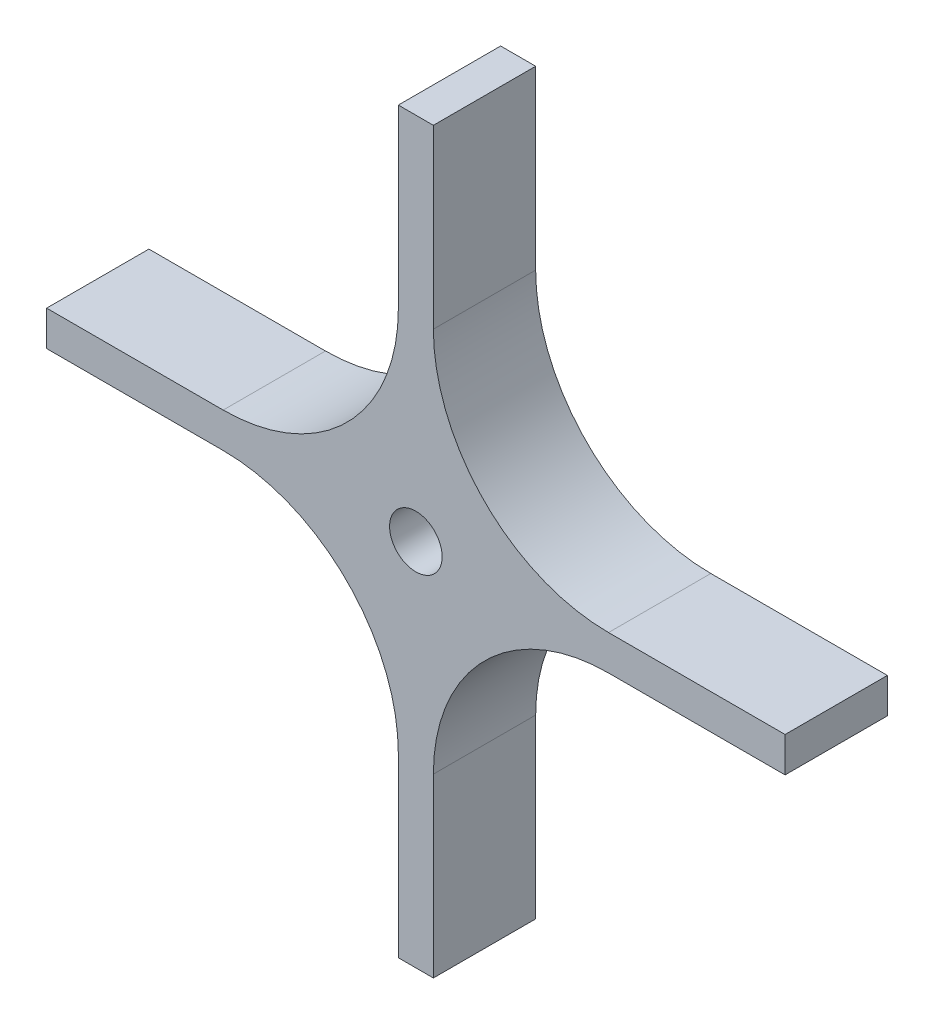
SolidWorks part; units mm, degrees
ref_plane "Front Plane" through (0, 0, 0) normal (0, 0, 1) x (1, 0, 0)
ref_plane "Top Plane" through (0, 0, 0) normal (0, 1, 0) x (1, 0, 0)
ref_plane "Right Plane" through (0, 0, 0) normal (1, 0, 0) x (0, 0, -1)
sketch "Sketch1" plane through (0, 0, 0) normal (0, 0, 1) x (1, 0, 0)
  line L0 (1.5875, -1.5875) -> (1.5875, -33.4645)
  line L1 (-1.5875, 33.4645) -> (1.5875, 33.4645)
  line L2 (-1.5875, 33.4645) -> (-1.5875, 1.5875)
  line L3 (-1.5875, -33.4645) -> (1.5875, -33.4645)
  line L4 (1.5875, 33.4645) -> (1.5875, 1.5875)
  line L5 (-1.5875, 33.4645) -> (1.5875, -33.4645) construction
  line L6 (-1.5875, -33.4645) -> (1.5875, 33.4645) construction
  line L7 (-33.4645, 1.5875) -> (-1.5875, 1.5875)
  line L8 (-33.4645, 1.5875) -> (-33.4645, -1.5875)
  line L9 (-33.4645, -1.5875) -> (-1.5875, -1.5875)
  line L10 (33.4645, 1.5875) -> (33.4645, -1.5875)
  line L11 (-33.4645, 1.5875) -> (33.4645, -1.5875) construction
  line L12 (-33.4645, -1.5875) -> (33.4645, 1.5875) construction
  line L13 (1.5875, -1.5875) -> (33.4645, -1.5875)
  line L14 (1.5875, 1.5875) -> (33.4645, 1.5875)
  line L15 (-1.5875, -1.5875) -> (-1.5875, -33.4645)
  circle A0 centre (17.526, 17.526) radius 15.9385 construction
  circle A1 centre (0, 0) radius 42.8625 construction
  point P0 (0, 0)
  point P6 (0, 0)
  point P21 (0, 0)
  point P22 (0, 0)
  dimension "D3" = 31.877
  dimension "D4" = 85.725
  dimension "D1" = 3.175
  dimension "D2" = 3.175
extrude "Boss-Extrude1" add sketch "Sketch1" along normal mid plane 9.271 contours L7 L2 L1 L4 L14 L10 L13 L0 L3 L15 L9 L8
fillet "Fillet1" radius 15.875 4 edges at (-1.5875, -1.5875, 0) (-1.5875, 1.5875, 0) (1.5875, -1.5875, 0) (1.5875, 1.5875, 0)
sketch "Sketch2" plane through (0, 0, 4.6355) normal (0, 0, 1) x (1, 0, 0)
  circle A0 centre (0, 0) radius 42.8625
hole_wizard "3/16 (0.1875) Diameter Hole1" positions "Sketch3" profile "Sketch4" hole size "3/16" standard "ANSI Inch" end condition through all
sketch "Sketch3" plane through (0, 0, 4.6355) normal (0, 0, 1) x (1, 0, 0)
  point P0 (0, 0)
sketch "Sketch4" plane through (0, 0, 4.6355) normal (1, 0, 0) x (0, -1, 0)
  line L0 (0, 0) -> (0, 9.271)
  line L1 (0, 9.271) -> (2.3812, 9.271)
  line L2 (2.3812, 9.271) -> (2.3812, 0)
  line L5 (2.3812, 0) -> (0, 0)
  line L11 (0, -6.35) -> (0, 107.95) construction
  dimension "Thru Hole Dia." = 4.7625
  dimension "Thru Hole Depth" = 9.271
